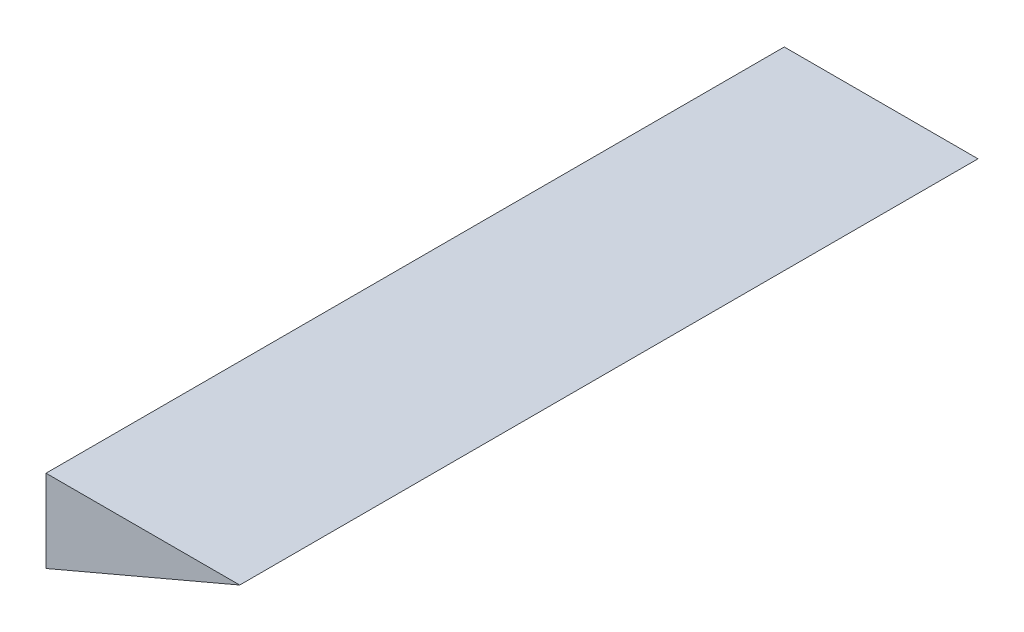
SolidWorks part; units mm, degrees
ref_plane "Ebene vorne" through (0, 0, 0) normal (0, 0, 1) x (1, 0, 0)
ref_plane "Ebene oben" through (0, 0, 0) normal (0, 1, 0) x (1, 0, 0)
ref_plane "Ebene rechts" through (0, 0, 0) normal (1, 0, 0) x (0, 0, -1)
sketch "Skizze1" plane through (0, 0, 0) normal (0, 0, 1) x (1, 0, 0)
  line L2 (-188.5516, 146.6266) -> (-188.5516, 124.273) construction
  line L3 (-188.5516, 146.6266) -> (-136.0693, 146.6266) construction
  line L6 (-188.5516, 146.6266) -> (-188.5516, 124.273)
  line L7 (-188.5516, 146.6266) -> (-136.0693, 146.6266)
  line L8 (-188.5516, 124.273) -> (-136.0693, 146.6266) construction
  line L9 (-188.5516, 124.273) -> (-136.0693, 146.6266)
extrude "Aufsatz-Linear austragen1" add sketch "Skizze1" along normal blind 200
